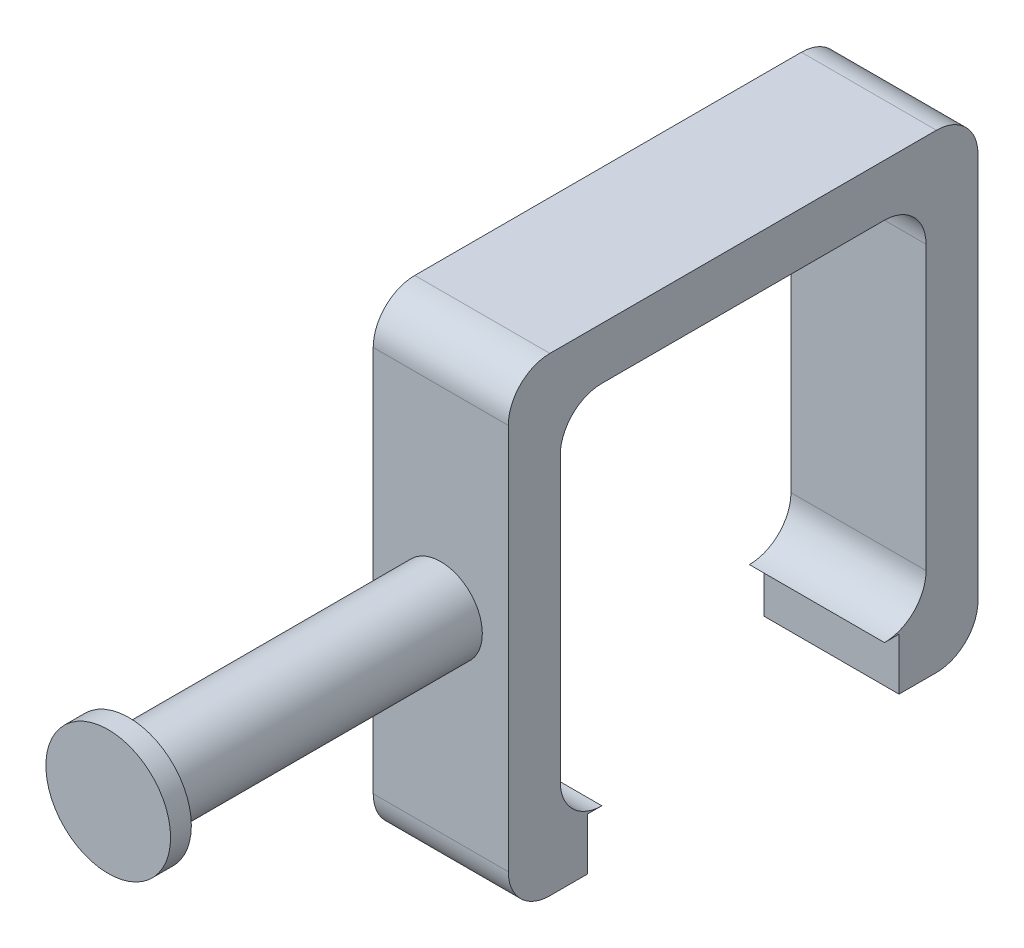
SolidWorks part; units mm, degrees
ref_plane "Front Plane" through (0, 0, 0) normal (0, 0, 1) x (1, 0, 0)
ref_plane "Top Plane" through (0, 0, 0) normal (0, 1, 0) x (1, 0, 0)
ref_plane "Right Plane" through (0, 0, 0) normal (1, 0, 0) x (0, 0, -1)
sketch "Sketch1" plane through (0, 0, 0) normal (1, 0, 0) x (0, 0, -1)
  line L1 (17.6, -17.6) -> (-17.6, -17.6)
  line L2 (17.6, -17.6) -> (17.6, 17.6)
  line L3 (17.6, 17.6) -> (-17.6, 17.6)
  line L4 (-17.6, -17.6) -> (-17.6, 17.6)
  line L5 (17.6, -17.6) -> (-17.6, 17.6) construction
  line L6 (17.6, 17.6) -> (-17.6, -17.6) construction
  line L7 (22.6, -22.6) -> (-22.6, -22.6)
  line L8 (22.6, -22.6) -> (22.6, 22.6)
  line L9 (22.6, 22.6) -> (-22.6, 22.6)
  line L10 (-22.6, -22.6) -> (-22.6, 22.6)
  line L11 (22.6, -22.6) -> (-22.6, 22.6) construction
  line L12 (22.6, 22.6) -> (-22.6, -22.6) construction
  point P0 (0, 0)
  point P6 (0, 0)
  dimension "D1" = 35.2
  dimension "D2" = 35.2
  dimension "D3" = 5
  dimension "D4" = 5
extrude "Boss-Extrude1" add sketch "Sketch1" against normal blind 13
fillet "Fillet1" radius 4 8 edges at (-6.5, -22.6, -22.6) (-6.5, -22.6, 22.6) (-6.5, 22.6, 22.6) (-6.5, 22.6, -22.6) (-6.5, -17.6, -17.6) (-6.5, 17.6, -17.6) (-6.5, -17.6, 17.6) (-6.5, 17.6, 17.6)
sketch "Sketch3" plane through (0, 0, 0) normal (1, 0, 0) x (0, 0, -1)
  line L0 (-15, -17.6) -> (-15, -22.6)
  line L1 (-13.6, -17.6) -> (13.6, -17.6) construction
  line L2 (-18.6, -22.6) -> (18.6, -22.6) construction
  line L3 (-15, -22.6) -> (15, -22.6)
  line L4 (15, -22.6) -> (15, -17.6)
  line L5 (15, -17.6) -> (-15, -17.6)
  point P6 (0, -22.6)
  dimension "D1" = 30
extrude "Cut-Extrude1" cut sketch "Sketch3" against normal through all
sketch "Sketch4" plane through (0, 0, 22.6) normal (0, 0, 1) x (1, 0, 0)
  line L0 (-13, 18.6) -> (0, 18.6) construction
  line L1 (0, 18.6) -> (-13, 18.6) construction
  line L2 (-13, 18.6) -> (-13, -18.6) construction
  line L3 (-6.5, 18.6) -> (-6.5, 0) construction
  line L4 (0, 18.6) -> (0, -18.6) construction
  circle A0 centre (-6.5, 0) radius 4
  point P1 (0, 0)
  point P9 (-5.0572, 6.8092)
  dimension "D1" = 8
extrude "Boss-Extrude2" add sketch "Sketch4" along normal blind 30
sketch "Sketch5" plane through (0, 0, 52.6) normal (0, 0, 1) x (1, 0, 0)
  circle A0 centre (-6.5, 0) radius 6
  circle A1 centre (-6.5, 0) radius 4 construction
  point P2 (0, 0)
  dimension "D1" = 12
extrude "Boss-Extrude3" add sketch "Sketch5" along normal blind 2
